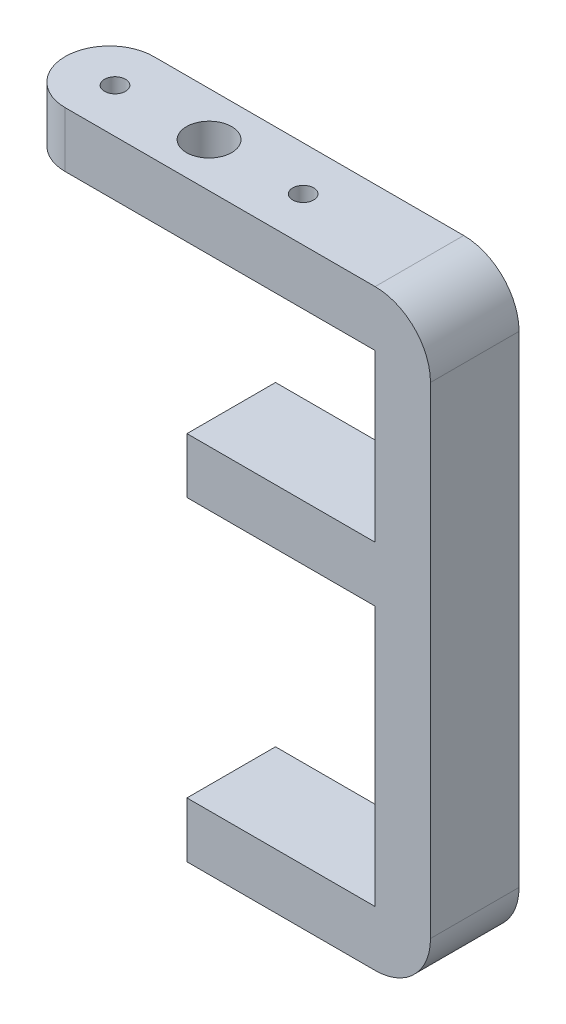
SolidWorks part; units mm, degrees
material "ABS"
ref_plane "Přední rovina" through (0, 0, 0) normal (0, 0, 1) x (1, 0, 0)
ref_plane "Horní rovina" through (0, 0, 0) normal (0, 1, 0) x (1, 0, 0)
ref_plane "Pravá rovina" through (0, 0, 0) normal (1, 0, 0) x (0, 0, -1)
sketch "Skica1" plane through (0, 0, 0) normal (0, 0, 1) x (1, 0, 0)
  line L0 (0, 0) -> (17, 0)
  line L1 (17, 0) -> (17, 23.5)
  line L2 (17, 23.5) -> (0, 23.5)
  line L3 (0, 23.5) -> (0, 28.5)
  line L4 (0, 28.5) -> (22, 28.5)
  line L5 (22, 28.5) -> (22, -5)
  line L6 (22, -5) -> (0, -5)
  line L7 (0, -5) -> (0, 0)
  dimension "D1" = 23.5
  dimension "D2" = 17
  dimension "D3" = 5
  dimension "D4" = 5
extrude "Přidat vysunutím1" add sketch "Skica1" along normal mid plane 8
sketch "Skica2" plane through (0, 28.5, 0) normal (0, 1, 0) x (1, 0, 0)
  line L0 (22, -4) -> (0, -4) construction
  line L1 (22, 4) -> (17, 4)
  line L2 (22, 4) -> (22, -4)
  line L3 (22, -4) -> (17, -4)
  line L4 (17, 4) -> (17, -4)
  dimension "D1" = 5
extrude "Přidat vysunutím2" add sketch "Skica2" along normal blind 20
sketch "Skica3" plane through (17, 0, 0) normal (-1, 0, 0) x (0, 0, 1)
  line L0 (-4, 48.5) -> (-4, 28.5) construction
  line L1 (4, 48.5) -> (-4, 48.5)
  line L2 (4, 48.5) -> (4, 43.5)
  line L3 (4, 43.5) -> (-4, 43.5)
  line L4 (-4, 48.5) -> (-4, 43.5)
  dimension "D1" = 5
extrude "Přidat vysunutím3" add sketch "Skica3" along normal blind 32
sketch "Skica5" plane through (0, 48.5, 0) normal (0, 1, 0) x (1, 0, 0)
  line L0 (-15, 0) -> (-2, 0) construction
  line L1 (-15, -4) -> (-15, 4) construction
  circle A0 centre (-2, 0) radius 2.04
  dimension "D1" = 4.08
  dimension "D2" = 13
extrude "Odebrat vysunutím1" cut sketch "Skica5" against normal blind 15
fillet "Zaoblit1" radius 5 2 edges at (22, -5, 0) (22, 48.5, 0)
sketch "Skica6" plane through (0, 0, 0) normal (-1, 0, 0) x (0, 0, 1)
  circle A0 centre (-0.0001, 25.0937) radius 1.2
  circle A1 centre (-0.0001, -1.8938) radius 1.2
  dimension "D1" = 2.4
extrude "Odebrat vysunutím2" cut sketch "Skica6" against normal blind 8
fillet "Zaoblit2" radius 4 2 edges at (-15, 46, -4) (-15, 46, 4)
sketch "Skica7" plane through (0, 48.5, 0) normal (0, 1, 0) x (1, 0, 0)
  line L0 (-10.5, 0) -> (6.5, 0) construction
  line L1 (6.5, 0) -> (0, 0) construction
  circle A0 centre (-10.5, 0) radius 0.95
  circle A1 centre (6.5, 0) radius 0.95
  circle A2 centre (-2, 0) radius 2.04 construction
  dimension "D1" = 1.9
  dimension "D2" = 17
  dimension "D3" = 8.5
extrude "Odebrat vysunutím3" cut sketch "Skica7" against normal blind 13
scale "Scale1" scale about centroid uniform scaling yes scale factor 8
equation "\"D3@Skica7\"=\"D2@Skica7\"/2"
